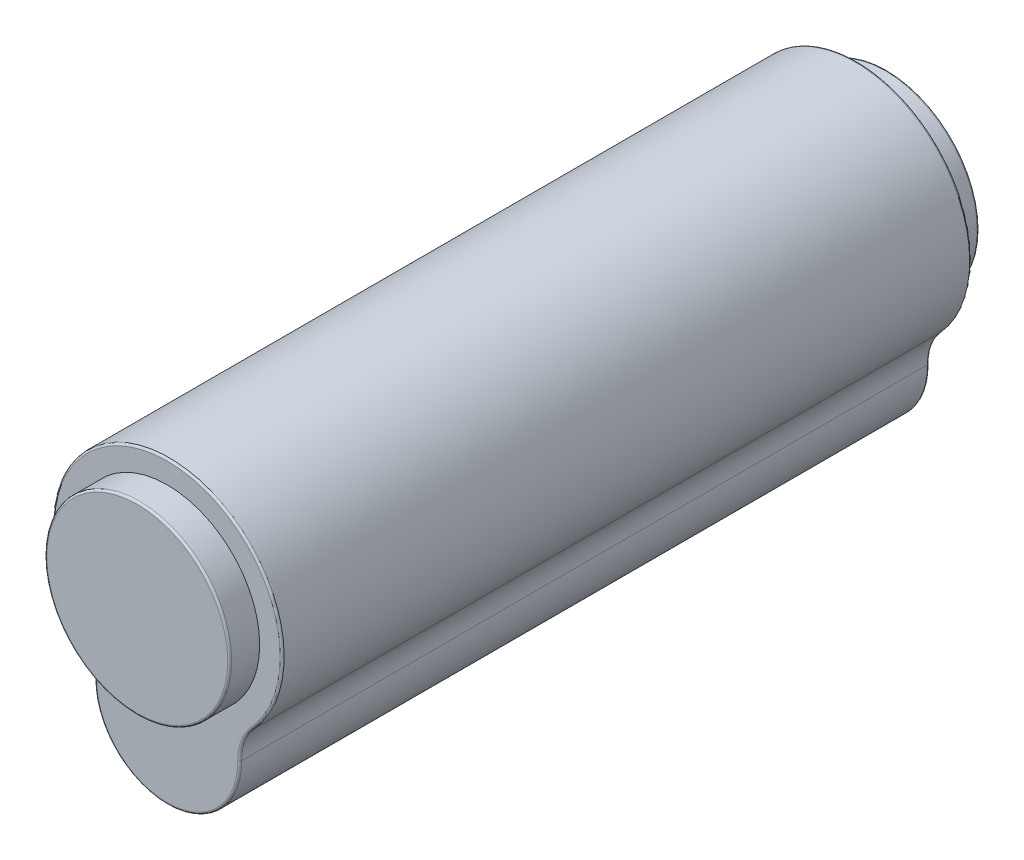
SolidWorks part; units mm, degrees
ref_plane "Plan de face" through (0, 0, 0) normal (0, 0, 1) x (1, 0, 0)
ref_plane "Plan de dessus" through (0, 0, 0) normal (0, 1, 0) x (1, 0, 0)
ref_plane "Plan de droite" through (0, 0, 0) normal (1, 0, 0) x (0, 0, -1)
sketch "Esquisse1" plane through (0, 0, 0) normal (0, 0, 1) x (1, 0, 0)
  arc A0 (-8.5368, -7.7054) -> (-7.2491, -11.1349) centre (-12.2485, -11.0556) cw
  arc A1 (8.5368, -7.7054) -> (-8.5368, -7.7054) centre (0, 0) ccw
  arc A2 (-7.2491, -11.1349) -> (7.2491, -11.1349) centre (0, -11.25) ccw
  arc A3 (7.2491, -11.1349) -> (8.5368, -7.7054) centre (12.2485, -11.0556) cw
  dimension "D1" = 5
extrude "Extrusion1" add sketch "Esquisse1" along normal blind 69
shell "Coque1" [suppressed] thickness 0.2
sketch "Esquisse2" plane through (0, 0, 69) normal (0, 0, 1) x (1, 0, 0)
  circle A0 centre (0, 0) radius 9.25
extrude "Boss.-Extru.1" add sketch "Esquisse2" along normal blind 3
sketch "Esquisse3" plane through (0, 0, 0) normal (0, 0, -1) x (-1, 0, 0)
  circle A0 centre (0, 0) radius 9.25
extrude "Boss.-Extru.2" add sketch "Esquisse3" along normal blind 3
fillet "Congé1" radius 0.2 10 edges at (7.5675, -9.298, 0) (0, -18.5, 0) (-7.5675, -9.298, 0) (7.5675, -9.298, 69) (0, -18.5, 69) (-7.5675, -9.298, 69) (-9.25, 0, -3) (0, 11.5, 0) (0, 11.5, 69) (9.25, 0, 72)
shell "Coque2" thickness 1
